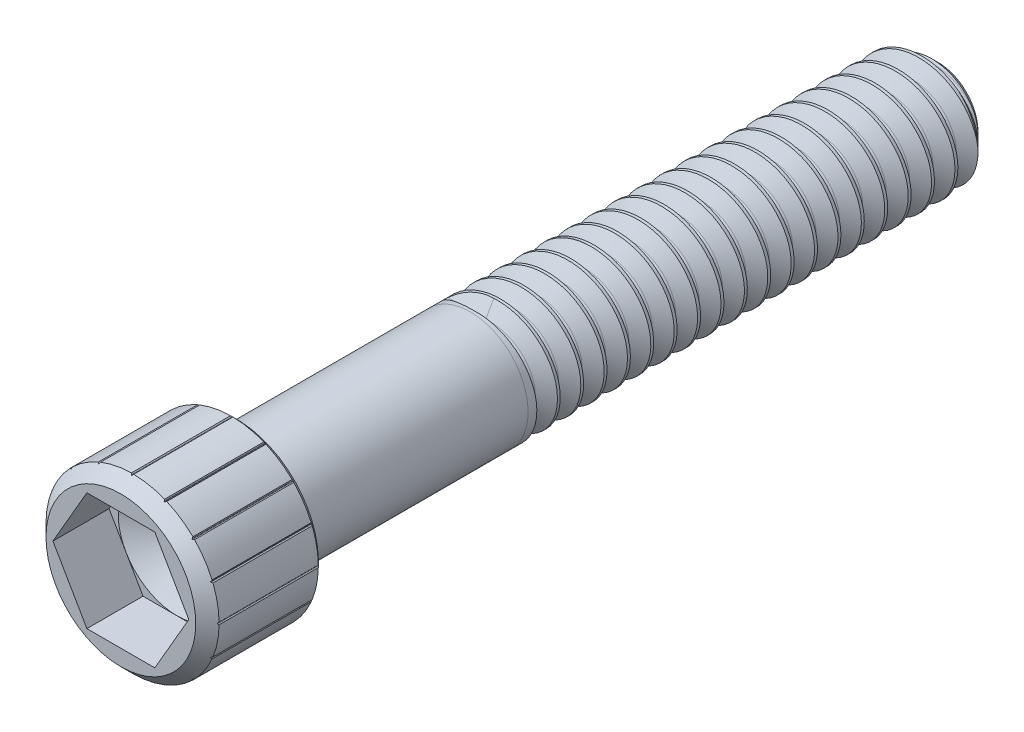
SolidWorks part; units mm, degrees
material "Alloy Steel (SS)"
ref_plane "Front Plane" through (0, 0, 0) normal (0, 0, 1) x (1, 0, 0)
ref_plane "Top Plane" through (0, 0, 0) normal (0, 1, 0) x (1, 0, 0)
ref_plane "Right Plane" through (0, 0, 0) normal (1, 0, 0) x (0, 0, -1)
sketch "Sketch1" plane through (0, 0, 0) normal (1, 0, 0) x (0, 0, -1)
  line L0 (4.8921, 0) -> (44.3738, 0)
  line L1 (0, 3.194) -> (0, 4.064)
  line L2 (6.2738, 3.3115) -> (6.2738, 4.445)
  line L3 (0.635, 4.699) -> (6.0198, 4.699)
  line L4 (-1000, 4.699) -> (49000, 4.699) construction
  line L5 (-1000, 0) -> (49000, 0) construction
  line L6 (44.3738, 0) -> (44.3738, 2.159)
  line L7 (0, -1000) -> (0, 49000) construction
  line L8 (6.2738, -1000) -> (6.2738, 49000) construction
  line L9 (44.3738, -1000) -> (44.3738, 49000) construction
  line L10 (0, 4.064) -> (0.635, 4.699)
  line L11 (6.2738, 4.445) -> (6.0198, 4.699)
  line L12 (0, 3.194) -> (3.048, 3.194)
  line L13 (0, 3.194) -> (44.3738, 3.194) construction
  line L14 (0, 0) -> (44.3738, 0) construction
  line L15 (25.3238, 3.1236) -> (43.4092, 3.1236)
  line L16 (3.048, 3.194) -> (4.8921, 0)
  line L17 (4.8921, 3.1236) -> (44.3738, 3.1236) construction
  line L19 (18.9738, 3.1337) -> (25.3238, 3.1236)
  line L21 (43.4092, 3.1236) -> (44.3738, 2.159)
  line L22 (6.4516, 3.1337) -> (18.9738, 3.1337)
  line L23 (4.8921, 3.1337) -> (44.3738, 3.1337) construction
  arc A0 (6.2738, 3.3115) -> (6.4516, 3.1337) centre (6.4516, 3.3115) ccw
  point P9 (0, 4.699)
  point P13 (6.2738, 4.699)
  dimension "D11" = 0.1778
  dimension "D1" = 6.2738
  dimension "D2" = 4.699
  dimension "D3" = 45
  dimension "D4" = 45
  dimension "D6" = 3.194
  dimension "D8" = 30
  dimension "D9" = 3.048
  dimension "D10" = 3.1337
  dimension "D12" = 6.35
  dimension "D13" = 19.05
  dimension "D14" = 45
  dimension "D15" = 3.1236
  dimension "D16" = 0.9646
  dimension "D17" = 0.092
  dimension "D5" = 0.635
  dimension "D7" = 0.254
revolve "Revolve1" add sketch "Sketch1" angle 360 about L0
sketch "Sketch2" plane through (0, 0, 0) normal (0, 0, 1) x (1, 0, 0)
  line L0 (-1.8441, 3.194) -> (1.8441, 3.194)
  line L1 (1.8441, 3.194) -> (3.6882, 0)
  line L2 (3.6882, 0) -> (1.8441, -3.194)
  line L3 (1.8441, -3.194) -> (-1.8441, -3.194)
  line L4 (-1.8441, -3.194) -> (-3.6882, 0)
  line L5 (-3.6882, 0) -> (-1.8441, 3.194)
  point P14 (0, 0)
  dimension "D2" = 6.3881
  dimension "D3" = 7.3763
  dimension "D1" = 6
extrude "Cut-Extrude1" cut sketch "Sketch2" against normal blind 3.048
sketch "Sketch3" plane through (0, 0, -44.3738) normal (0, 0, -1) x (-1, 0, 0)
  circle A0 centre (0, 0) radius 3.1337
  circle A1 centre (0, 0) radius 2.159 construction
  dimension "D1" = 6.2674
curve "Helix/Spiral1" pitch 1.27 height 25.4 turns 20
sketch "Sketch4" plane through (0, 0, 0) normal (1, 0, 0) x (0, 0, -1)
  line L0 (44.3738, 3.1236) -> (44.5325, 3.1236) construction
  line L1 (45.207, 2.3669) -> (45.0882, 2.1612) construction
  line L2 (44.3738, 3.1236) -> (44.4532, 3.261) construction
  line L3 (44.9294, 2.4362) -> (45.2469, 2.4362) construction
  line L4 (44.4532, 3.261) -> (44.5325, 3.1236) construction
  line L5 (45.0882, 2.1612) -> (44.9694, 2.3669) construction
  line L6 (44.5118, 3.1594) -> (44.9694, 2.3669)
  line L7 (45.207, 2.3669) -> (45.6645, 3.1594)
  line L8 (44.5118, 3.1594) -> (45.6645, 3.1594)
  line L9 (44.3738, 2.159) -> (44.3738, -2.159) construction
  arc A0 (44.9694, 2.3669) -> (45.207, 2.3669) centre (45.0882, 2.4355) ccw
  dimension "D9" = 0.1372
  dimension "D2" = 1.0999
  dimension "D3" = 0.1375
  dimension "D4" = 0.3175
  dimension "D5" = 0.275
  dimension "D6" = 1.1527
  dimension "D7" = 0.7144
  dimension "D8" = 60
  dimension "D10" = 0.7233
  dimension "D11" = 0.0692
  dimension "D13" = 0.1587
sweep "Cut-Sweep1" cut profiles "Sketch4" path "Helix/Spiral1"
sketch "Sketch5" plane through (0, 0, 0) normal (1, 0, 0) x (0, 0, -1)
  line L3 (19.1268, 3.1335) -> (19.5694, 2.3669)
  line L4 (19.807, 2.3669) -> (20.2485, 3.1317)
  line L5 (20.2485, 3.1317) -> (19.1268, 3.1335)
  line L6 (19.1268, 3.1335) -> (19.5694, 2.3669)
  line L7 (19.807, 2.3669) -> (20.2485, 3.1317)
  line L8 (20.2485, 3.1317) -> (19.1268, 3.1335)
  arc A1 (19.5694, 2.3669) -> (19.807, 2.3669) centre (19.6882, 2.4355) ccw
  arc A2 (19.5694, 2.3669) -> (19.807, 2.3669) centre (19.6882, 2.4355) ccw
  dimension "D1" = 0
extrude "Cut-Extrude2" cut sketch "Sketch5" against normal through all
sketch "Sketch6" plane through (0, 0, 0) normal (0, 0, 1) x (1, 0, 0)
  line L0 (0, 3.194) -> (0, 0) construction
  line L1 (0.018, 4.6535) -> (0.0631, 4.6986)
  line L2 (-0.0631, 4.6986) -> (-0.018, 4.6535)
  line L3 (1.8441, 3.194) -> (-1.8441, 3.194) construction
  arc A0 (0.018, 4.6535) -> (-0.018, 4.6535) centre (0, 4.6714) cw
  arc A3 (0.0631, 4.6986) -> (-0.0631, 4.6986) centre (0, 0) ccw
  point P11 (0, 4.6355)
  dimension "D1" = 4.699
  dimension "D3" = 0.0254
  dimension "D2" = 0.0631
extrude "Cut-Extrude3" cut sketch "Sketch6" against normal up to next
pattern_circular "CirPattern1" count 16 over 360 about axis through (0, 0, 0) along (0, 0, 1) of "Cut-Extrude3"
equation "\"P\"= .05in"
equation "\"H\"= \"P\" * cos ( 30deg )"
equation "\"D13@Sketch4\" = .125 * \"P\""
equation "\"D2@Sketch4\" = \"H\""
equation "\"D3@Sketch4\" = .125 * \"H\""
equation "\"D5@Sketch4\" = .25 * \"H\""
equation "\"D4@Sketch4\" = .25 * \"P\""
equation "\"D9@Sketch4\" = .108 * \"P\""
